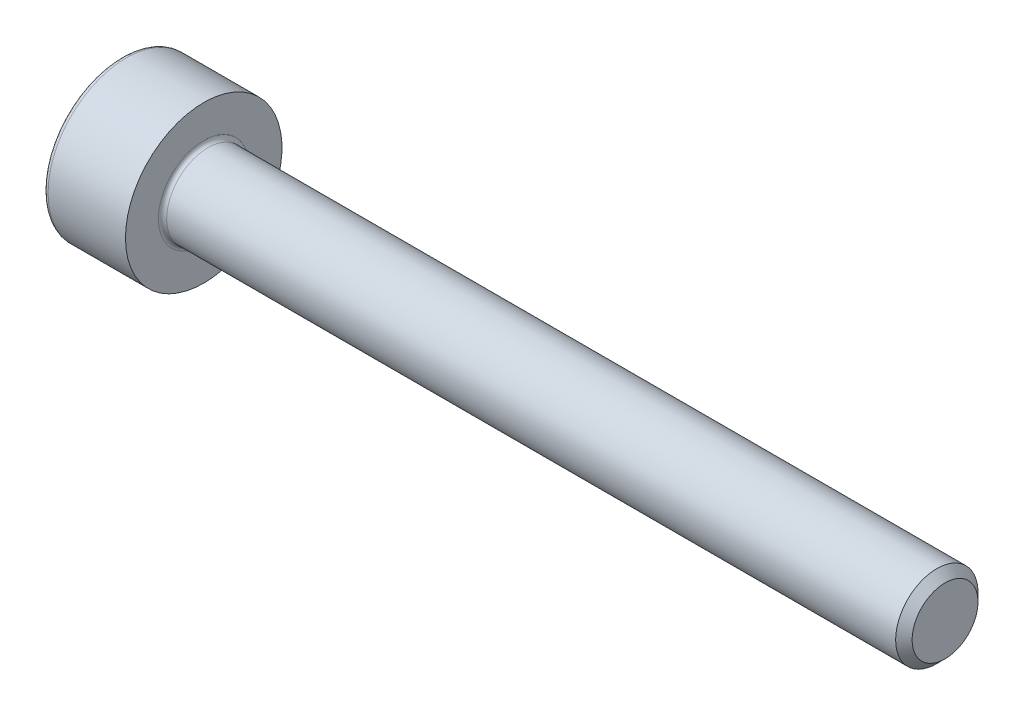
SolidWorks part; units mm, degrees
ref_plane "Front Plane" through (0, 0, 0) normal (0, 0, 1) x (1, 0, 0)
ref_plane "Top Plane" through (0, 0, 0) normal (0, 1, 0) x (1, 0, 0)
ref_plane "Right Plane" through (0, 0, 0) normal (1, 0, 0) x (0, 0, -1)
sketch "Sketch1" plane through (0, 0, 0) normal (0, 0, 1) x (1, 0, 0)
  line L0 (0, 0) -> (0, 1.9)
  line L1 (0, 1.9) -> (2, 1.9)
  line L2 (2, 1.9) -> (2, 0)
  line L3 (0, 0) -> (4.2799, 0) construction
  line L4 (2, 0) -> (20, 0)
  line L5 (20, 0) -> (20, 1)
  line L6 (20, 1) -> (2, 1)
  dimension "D1" = 18
revolve "Revolve1" add sketch "Sketch1" angle 360 about L3 region at (1, 0.95, 0) region at (11, 0.5, 0)
fillet "Fillet1" radius 0.1 1 edges at (2, 0, 1)
fillet "Fillet2" radius 0.12 1 edges at (0, 0, 1.9)
chamfer "Chamfer1" distance 0.2 angle 45 1 edges at (20, 0, 1)
sketch "Sketch2" plane through (0, 0, 0) normal (-1, 0, 0) x (0, 0, 1)
  line L1 (0, 0.866) -> (-0.75, 0.433)
  line L2 (-0.75, 0.433) -> (-0.75, -0.433)
  line L3 (-0.75, -0.433) -> (0, -0.866)
  line L4 (0, -0.866) -> (0.75, -0.433)
  line L5 (0.75, -0.433) -> (0.75, 0.433)
  line L6 (0.75, 0.433) -> (0, 0.866)
  circle A0 centre (0, 0) radius 0.75 construction
extrude "Extrude1" cut sketch "Sketch2" against normal blind 1
